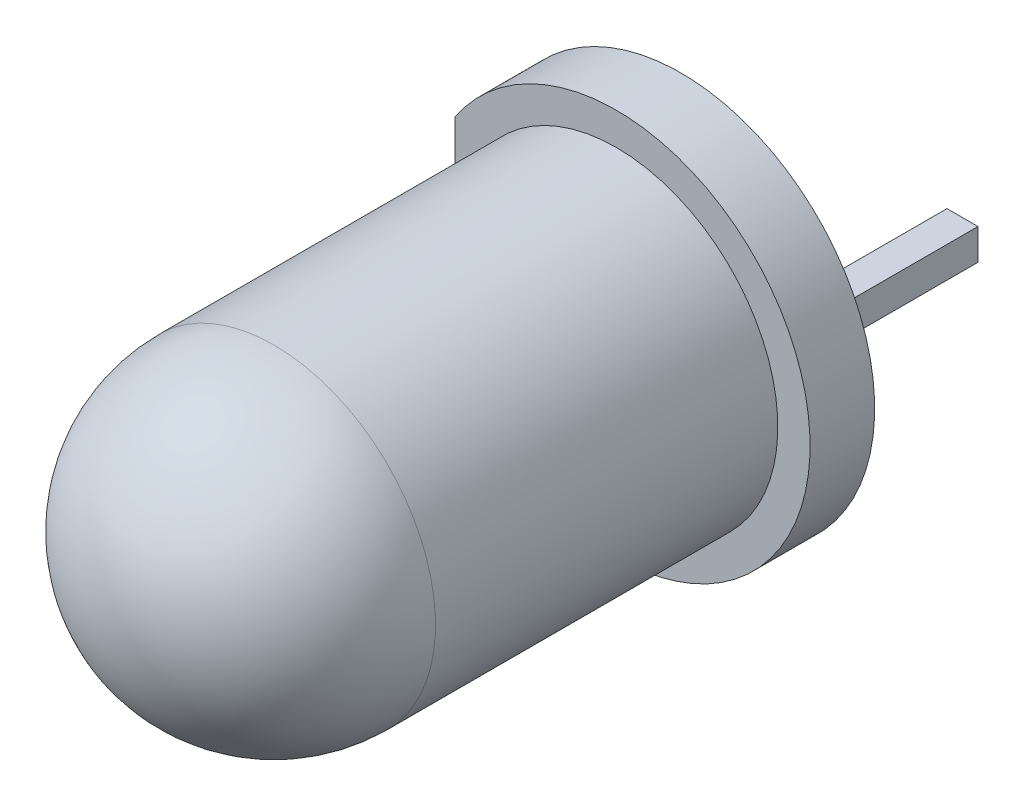
SolidWorks part; units mm, degrees
ref_plane "Plano frontal" through (0, 0, 0) normal (0, 0, 1) x (1, 0, 0)
ref_plane "Plano superior" through (0, 0, 0) normal (0, 1, 0) x (1, 0, 0)
ref_plane "Plano direito" through (0, 0, 0) normal (1, 0, 0) x (0, 0, -1)
sketch "Esboço1" plane through (0, 0, 0) normal (0, 0, 1) x (1, 0, 0)
  circle A0 centre (0, 0) radius 3
  dimension "D1" = 6
extrude "Ressalto-extrusão1" add sketch "Esboço1" along normal blind 1
sketch "Esboço3" plane through (0, 0, 0) normal (1, 0, 0) x (0, 0, -1)
  line L0 (-1, 0) -> (-8.8, 0)
  line L1 (-1, 3) -> (-1, -3) construction
  line L2 (-6.3, 2.5) -> (-1, 2.5)
  line L3 (-1, 0) -> (-1, 2.5)
  arc A0 (-8.8, 0) -> (-6.3, 2.5) centre (-6.3, 0) cw
  dimension "D1" = 2.5
  dimension "D2" = 7.8
revolve "Revolução1" add sketch "Esboço3" angle 360 about L0
sketch "Esboço4" plane through (0, 0, 0) normal (0, 0, -1) x (-1, 0, 0)
  line L0 (2.5, 1.6583) -> (2.5, -1.6583)
  circle A0 centre (0, 0) radius 3 construction
  arc A1 (2.5, -1.6583) -> (2.5, 1.6583) centre (0, 0) ccw
  circle A2 centre (0, 0) radius 2.5 construction
extrude "Corte-extrusão1" cut sketch "Esboço4" against normal up to surface (1 mm away) up to face at (2.5, 0, 1)
sketch "Esboço5" plane through (0, 0, 0) normal (0, 0, -1) x (-1, 0, 0)
  line L0 (-1.12, 0) -> (1.12, 0) construction
  line L1 (-1.6, -0.24) -> (-1.12, -0.24)
  line L2 (-1.6, -0.24) -> (-1.6, 0.24)
  line L3 (-1.6, 0.24) -> (-1.12, 0.24)
  line L4 (-1.12, -0.24) -> (-1.12, 0.24)
  line L5 (1.12, -0.24) -> (1.6, -0.24)
  line L6 (1.12, -0.24) -> (1.12, 0.24)
  line L7 (1.12, 0.24) -> (1.6, 0.24)
  line L8 (1.6, -0.24) -> (1.6, 0.24)
  dimension "D1" = 3.2
  dimension "D2" = 0.48
extrude "Ressalto-extrusão2" add sketch "Esboço5" along normal blind 1 separate body
sketch "Esboço6" plane through (0, 0, -1) normal (0, 0, -1) x (-1, 0, 0)
  line L4 (-1.6, 0.24) -> (-1.6, -0.24)
  line L5 (-1.6, -0.24) -> (-1.12, -0.24)
  line L6 (-1.12, -0.24) -> (-1.12, 0.24)
  line L7 (-1.12, 0.24) -> (-1.6, 0.24)
  line L8 (-1.6, 0.24) -> (-1.6, -0.24)
  line L9 (-1.6, -0.24) -> (-1.12, -0.24)
  line L10 (-1.12, -0.24) -> (-1.12, 0.24)
  line L11 (-1.12, 0.24) -> (-1.6, 0.24)
  dimension "D1" = 0
extrude "Ressalto-extrusão3" add sketch "Esboço6" along normal blind 2 separate body
sketch "Esboço7" plane through (0, 0, 0) normal (0, 1, 0) x (1, 0, 0)
  line L0 (-1.6, 0) -> (-1.6, -3.5)
  line L1 (-1.12, 0) -> (-1.12, -2)
  line L2 (0.02, -2) -> (1.2, -4)
  line L3 (1.2, -4) -> (-1.3, -4)
  line L4 (-1.3, -4) -> (-1.6, -3.5)
  line L5 (-1.12, -2) -> (0.02, -2)
  line L6 (1.6, 0) -> (1.6, -4)
  line L7 (1.6, -4) -> (1.4, -4)
  line L8 (1.4, -4) -> (0.22, -2)
  line L9 (0.22, -2) -> (1.12, -2)
  line L10 (1.12, -2) -> (1.12, 0)
  line L11 (-1.6, 0) -> (-1.12, 0)
  line L12 (1.12, 0) -> (1.6, 0)
  dimension "D1" = 4
  dimension "D2" = 2
  dimension "D3" = 2.8
  dimension "D4" = 0.2
  dimension "D5" = 0.9
  dimension "D6" = 3.5
  dimension "D7" = 2.5
extrude "Corte-extrusão2" cut sketch "Esboço7" against normal mid plane 0.48
sketch "Esboço8" plane through (0, 0, 0) normal (0, 1, 0) x (1, 0, 0)
  line L0 (-1.3, -4) -> (1.2, -4) construction
  line L1 (-1.6, -3.5) -> (-1.3, -4) construction
  line L2 (-1.6, 0) -> (-1.6, -3.5) construction
  line L3 (1.2, -4) -> (0.02, -2) construction
  line L4 (0.02, -2) -> (-1.12, -2) construction
  line L5 (-1.12, -2) -> (-1.12, 0) construction
  line L6 (0.22, -2) -> (1.4, -4) construction
  line L7 (1.12, -2) -> (0.22, -2) construction
  line L8 (1.12, 0) -> (1.12, -2) construction
  line L9 (1.6, -4) -> (1.6, 0) construction
  line L10 (1.4, -4) -> (1.6, -4) construction
  line L11 (-1.12, 0) -> (-1.6, 0) construction
  line L12 (1.6, 0) -> (1.12, 0) construction
  line L13 (-1.3, -4) -> (1.2, -4)
  line L14 (-1.6, -3.5) -> (-1.3, -4)
  line L15 (-1.6, 0) -> (-1.6, -3.5)
  line L16 (1.2, -4) -> (0.02, -2)
  line L17 (0.02, -2) -> (-1.12, -2)
  line L18 (-1.12, -2) -> (-1.12, 0)
  line L19 (0.22, -2) -> (1.4, -4)
  line L20 (1.12, -2) -> (0.22, -2)
  line L21 (1.12, 0) -> (1.12, -2)
  line L22 (1.6, -4) -> (1.6, 0)
  line L23 (1.4, -4) -> (1.6, -4)
  line L24 (-1.12, 0) -> (-1.6, 0)
  line L25 (1.6, 0) -> (1.12, 0)
extrude "Ressalto-extrusão4" add sketch "Esboço8" along normal mid plane 0.48 separate body
combine bodies "Combinar1" operation type add bodies to combine 109 106 104
combine bodies "Combinar2" operation type add bodies to combine 108 105
sketch "Esboço10" plane through (0, 0, 0) normal (0, 1, 0) x (1, 0, 0)
  line L0 (-0.05, -4) -> (-0.05, -3.7)
  line L1 (-1.3, -4) -> (1.2, -4) construction
  line L2 (-0.55, -4) -> (-0.05, -4)
  arc A0 (-0.05, -3.7) -> (-0.55, -4) centre (-0.05, -4.2667) ccw
  dimension "D1" = 0.5
  dimension "D2" = 0.3
revolve "Corte-Revolução1" cut sketch "Esboço10" angle 360 about L0
sketch "Esboço11" plane through (0, 0, 0) normal (0, 1, 0) x (1, 0, 0)
  line L0 (-0.55, -4) -> (-0.05, -4) construction
  line L1 (-0.05, -4) -> (-0.05, -3.7) construction
  line L2 (-0.55, -4) -> (-0.05, -4)
  line L3 (-0.05, -4) -> (-0.05, -3.7)
  arc A0 (-0.05, -3.7) -> (-0.55, -4) centre (-0.05, -4.2667) ccw construction
  arc A1 (-0.05, -3.7) -> (-0.55, -4) centre (-0.05, -4.2667) ccw
revolve "Revolução2" add sketch "Esboço11" angle 360 about L3
combine bodies "Combinar3" operation type add bodies to combine 113 112
sketch "Esboço12" plane through (0, 0, 4) normal (0, 0, 1) x (1, 0, 0)
  circle A0 centre (-0.05, 0) radius 0.2
  arc A1 (0.3886, 0.24) -> (-0.4886, 0.24) centre (-0.05, 0) ccw construction
  dimension "D1" = 0.4
extrude "Corte-extrusão3" cut sketch "Esboço12" against normal blind 0.1
sketch "Esboço13" plane through (0, 0, 0) normal (0, 1, 0) x (1, 0, 0)
  line L0 (1.6, 3) -> (-7.0603, 8)
  line L1 (1.6, 3) -> (1.12, 3) construction
  dimension "D1" = 10
  dimension "D2" = 30
ref_plane "Plano1" through (1.699, 0, -2.9428) normal (0.5, 0, -0.866) x (-0.866, 0, -0.5)
